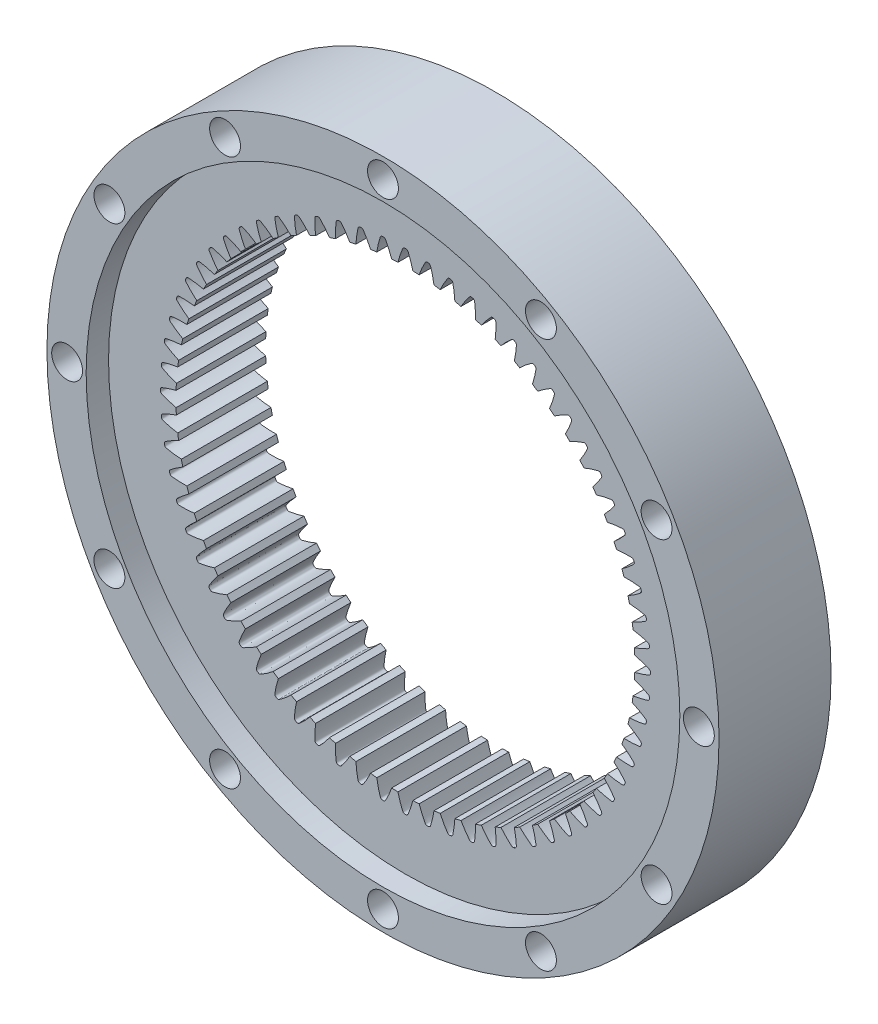
SolidWorks part; units mm, degrees
ref_plane "Front Plane" through (0, 0, 0) normal (0, 0, 1) x (1, 0, 0)
ref_plane "Top Plane" through (0, 0, 0) normal (0, 1, 0) x (1, 0, 0)
ref_plane "Right Plane" through (0, 0, 0) normal (1, 0, 0) x (0, 0, -1)
ref_axis "Axis1" through (0, 0, 55) along (0, 0, -1)
sketch "SketchRevolveRing_Gear_Follower01" plane through (0, 0, 0) normal (1, 0, 0) x (0, 0, -1)
  line L0 (0, 0) -> (25.4, 0) construction
  line L1 (-6.35, 26.0117) -> (-6.35, 38.1)
  line L2 (-6.35, 38.1) -> (6.35, 38.1)
  line L3 (6.35, 38.1) -> (6.35, 26.0117)
  line L4 (6.35, 26.0117) -> (-6.35, 26.0117)
  dimension "Side1" = 6.35
  dimension "OutsideRadius" = 38.1
  dimension "Side2" = 6.35
  dimension "MinorDiameter" = 26.0117
revolve "Ring_Gear_Follower01" add sketch "SketchRevolveRing_Gear_Follower01" angle 360 about L0
sketch "SketchToothRing_Gear_Follower01" plane through (0, 0, 0) normal (0, 0, 1) x (1, 0, 0)
  arc A0 (25.8416, -0.8773) -> (25.8416, 0.8773) centre (0, 0) ccw
  spline S0 degree 3 poles (25.8416, 0.8773) (25.9339, 0.8591) (26.0778, 0.8272) (26.276, 0.7765) (26.4414, 0.7304) (26.6175, 0.677) (26.8039, 0.6161) (27.0003, 0.5467) (27.2075, 0.4702) (27.4312, 0.3737) (27.6084, 0.3185) (27.7032, 0.2508) (27.7274, 0.2266) (27.748, 0.1994) (27.7644, 0.1694) (27.7804, 0.1272) (27.786, 0.0815) (27.7851, 0.0356) (27.7854, 0) (27.7851, -0.0356) (27.786, -0.0815) (27.7804, -0.1272) (27.7644, -0.1694) (27.748, -0.1994) (27.7274, -0.2266) (27.7032, -0.2508) (27.6084, -0.3185) (27.4312, -0.3737) (27.2075, -0.4702) (27.0003, -0.5467) (26.8039, -0.6161) (26.6175, -0.677) (26.4414, -0.7304) (26.276, -0.7765) (26.0778, -0.8272) (25.9339, -0.8591) (25.8416, -0.8773) knots 0 0 0 0 0.062937 0.098485 0.136754 0.177743 0.221452 0.267881 0.31703 0.3689 0.431324 0.438915 0.446506 0.454098 0.461689 0.46928 0.484155 0.492078 0.5 0.507922 0.515845 0.53072 0.538311 0.545902 0.553494 0.561085 0.568676 0.6311 0.68297 0.732119 0.778548 0.822257 0.863246 0.901515 0.937063 1 1 1 1
extrude "ToothExtrudeCutRing_Gear_Follower01" cut sketch "SketchToothRing_Gear_Follower01" against normal blind 6.35 and the other way blind 6.35
ref_axis "Axis2" through (41.91, 0, 0) along (-1, 0, 0)
ref_plane "Plane1" through (0, 0, 0) normal (0, 0, -1) x (1, 0, 0)
pattern_circular "PatternRing_Gear_Follower01" count 68 every 5.294 about axis through (0, 0, 55) along (0, 0, -1) of "ToothExtrudeCutRing_Gear_Follower01"
sketch "AuxiliarySketchRing_Gear_Follower01" plane through (0, 0, 0) normal (0, 0, 1) x (1, 0, 0)
  circle A0 centre (0, 0) radius 26.8 construction
  circle A1 centre (0, 0) radius 25.1837 construction
  circle A2 centre (0, 0) radius 27.7853 construction
  circle A3 centre (0, 0) radius 26.0117 construction
  dimension "PitchDiameter" = 53.6
  dimension "BaseDiameter" = 50.3675
  dimension "MajorDiameter" = 55.5706
  dimension "MinorDiameter" = 52.0235
sketch "Sketch1" plane through (0, 0, 6.35) normal (0, 0, 1) x (1, 0, 0)
  circle A0 centre (0, 0) radius 33.655 construction
  circle A1 centre (0, 0) radius 34.925 construction
  circle A2 centre (0, 0) radius 28.575 construction
  circle A3 centre (0, 0) radius 33.655
  dimension "D1" = 67.31
  dimension "D2" = 69.85
  dimension "D3" = 57.15
extrude "Cut-Extrude1" cut sketch "Sketch1" against normal blind 2.54
sketch "Sketch2" plane through (0, 0, 6.35) normal (0, 0, 1) x (1, 0, 0)
  line L0 (0, 0) -> (0, 41.5527) construction
  circle A0 centre (0, 0) radius 35.814 construction
  circle A1 centre (0, 35.814) radius 1.75
  circle A2 centre (17.907, 31.0158) radius 1.75
  circle A3 centre (31.0158, 17.907) radius 1.75
  circle A4 centre (35.814, 0) radius 1.75
  circle A5 centre (31.0158, -17.907) radius 1.75
  circle A6 centre (17.907, -31.0158) radius 1.75
  circle A7 centre (0, -35.814) radius 1.75
  circle A8 centre (-17.907, -31.0158) radius 1.75
  circle A9 centre (-31.0158, -17.907) radius 1.75
  circle A10 centre (-35.814, 0) radius 1.75
  circle A11 centre (-31.0158, 17.907) radius 1.75
  circle A12 centre (-17.907, 31.0158) radius 1.75
  point P30 (0, 0)
  dimension "D1" = 71.628
  dimension "D2" = 3.5
  dimension "D3" = 12
extrude "Cut-Extrude2" cut sketch "Sketch2" against normal through all
